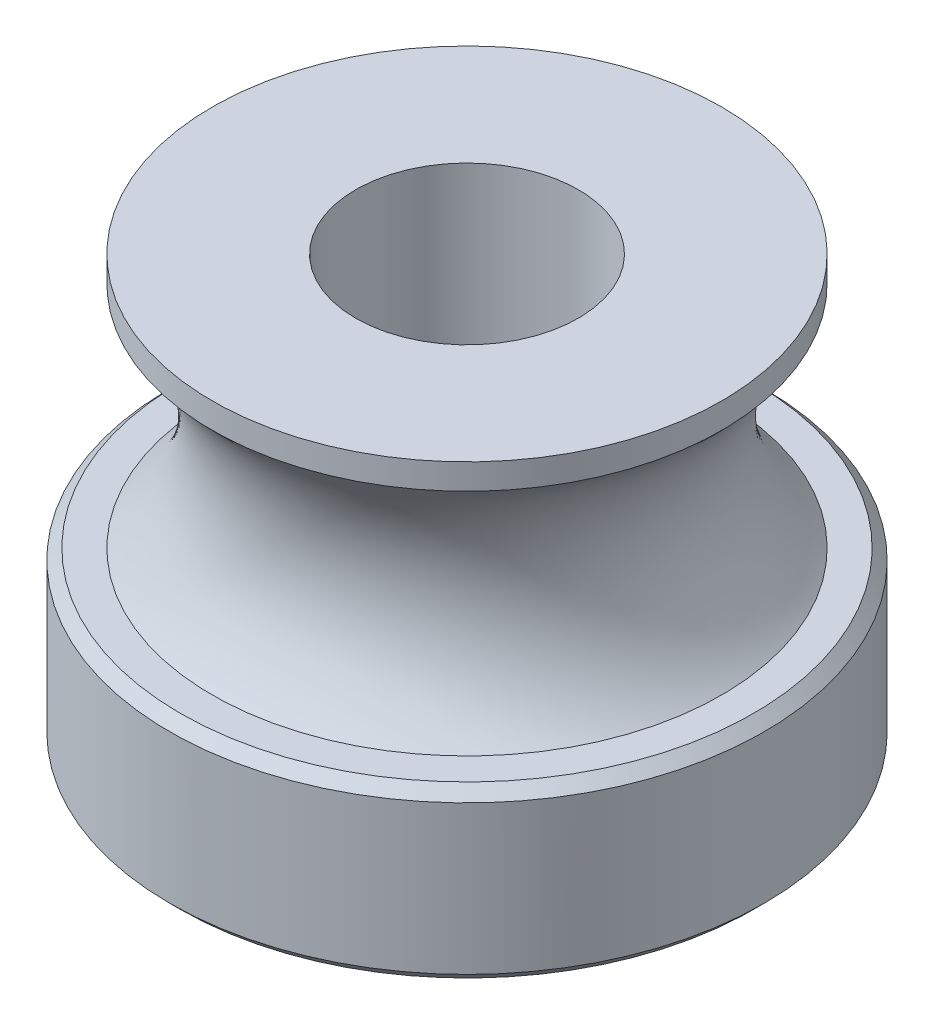
SolidWorks part; units mm, degrees
material "Brass"
ref_plane "Front Plane" through (0, 0, 0) normal (0, 0, 1) x (1, 0, 0)
ref_plane "Top Plane" through (0, 0, 0) normal (0, 1, 0) x (1, 0, 0)
ref_plane "Right Plane" through (0, 0, 0) normal (1, 0, 0) x (0, 0, -1)
sketch "Sketch1" plane through (0, 0, 0) normal (0, 0, 1) x (1, 0, 0)
  line L0 (0, 0) -> (0, 7.9375) construction
  line L1 (0, 7.9375) -> (-4.7625, 7.9375)
  line L2 (-5.5562, 3.175) -> (-5.5562, 0)
  line L3 (-5.5562, 0) -> (0, 0)
  line L4 (0, 0) -> (0, 7.9375)
  line L5 (0, 0) -> (0, -2.6189) construction
  line L6 (-3.81, 3.175) -> (-3.81, 7.9375) construction
  line L7 (-5.5562, 3.175) -> (-4.7625, 3.175)
  line L10 (-4.7625, 7.9375) -> (-4.7625, 7.4612)
  arc A0 (-4.7625, 3.175) -> (-4.7625, 7.4612) centre (-6.6973, 5.3181) ccw
  point P1 (0, 3.9688)
  dimension "D1" = 0.4763
  dimension "D2" = 0.9525
revolve "Revolve1" add sketch "Sketch1" angle 360 about L0
sketch "Sketch3" plane through (0, 0, 0) normal (0, 1, 0) x (1, 0, 0)
  circle A0 centre (0, 0) radius 2.0828
extrude "Cut-Extrude1" cut sketch "Sketch3" along normal through all
sketch "Sketch4" plane through (0, 0, 0) normal (0, 1, 0) x (1, 0, 0)
  circle A1 centre (0, 0) radius 2.0828
  circle A2 centre (0, 0) radius 2.0828
  dimension "D1" = 0
curve "Helix/Spiral1" pitch 0.7937 height 14.2875 turns 18 parameters "pitch"=0.7937
sketch "Sketch21" plane through (0, 0, 0) normal (0, 1, 0) x (1, 0, 0)
  line L0 (0, 2.0828) -> (0, 5.5562)
  circle A0 centre (0, 0) radius 5.5562 construction
  circle A1 centre (0, 0) radius 2.0828 construction
  circle A2 centre (0, 0) radius 5.5562 construction
  circle A3 centre (0, 0) radius 2.0828 construction
  dimension "D1" = 3.4734
sketch "Sketch5" plane through (0, 0, 0) normal (1, 0, 0) x (0, 0, -1)
  line L0 (-2.0828, 0) -> (-2.0828, -0.6945)
  line L1 (-2.0828, -0.6945) -> (-1.5672, -0.3969)
  line L2 (-1.5672, -0.3969) -> (-1.5672, -0.2977)
  line L3 (-1.5672, -0.2977) -> (-2.0828, 0)
  line L4 (-1.5672, -0.3473) -> (-2.0828, -0.3473) construction
  line L5 (-1.825, -0.5457) -> (-1.825, -0.1488) construction
  line L6 (2.0828, 0) -> (-2.0828, 0) construction
  dimension "D1" = 0.0992
  dimension "D2" = 0.3969
  dimension "D3" = 60
sweep "Sweep1" [suppressed] add profiles "Sketch5" path "Helix/Spiral1"
sketch "Sketch13" plane through (0, 0, 0) normal (0, -1, 0) x (1, 0, 0)
  circle A1 centre (0, 0) radius 5.5562
  circle A2 centre (0, 0) radius 5.5562
  dimension "D1" = 0
extrude "Cut-Extrude2" [suppressed] cut sketch "Sketch13" along normal through all
sketch "Sketch14" plane through (0, 7.9375, 0) normal (0, 1, 0) x (1, 0, 0)
  circle A0 centre (0, 0) radius 5.5562 construction
  circle A1 centre (0, 0) radius 5.5562
extrude "Cut-Extrude3" [suppressed] cut sketch "Sketch14" along normal through all
sketch "Sketch15" plane through (0, 0, 0) normal (0, -1, 0) x (1, 0, 0)
  circle A0 centre (0, 0) radius 2.0828 construction
  circle A1 centre (0, 0) radius 2.0828
extrude "Cut-Extrude4" [suppressed] cut sketch "Sketch15" against normal through all draft 45
sketch "Sketch16" plane through (0, 7.9375, 0) normal (0, 1, 0) x (1, 0, 0)
  circle A0 centre (0, 0) radius 2.0828 construction
  circle A1 centre (0, 0) radius 2.0828
extrude "Cut-Extrude5" [suppressed] cut sketch "Sketch16" against normal through all draft 45
chamfer "Chamfer1" distance 0.1984 angle 45 2 edges at (0, 3.175, -5.5562) (0, 0, -5.5562)
sketch "Sketch11" [suppressed] plane through (0, 0, 0) normal (0, 0, 1) x (1, 0, 0)
  line L0 (-2.0828, 7.9375) -> (-2.0828, 0)
  line L1 (2.0828, 7.9375) -> (2.0828, 0)
  line L2 (4.7625, 7.9375) -> (-4.7625, 7.9375) construction
  line L4 (-2.0828, 0) -> (2.0828, 0) construction
  dimension "D1" = 4.1656
sketch "Sketch12" plane through (0, 0, 0) normal (1, 0, 0) x (0, 0, -1)
  line L0 (-2.0828, 7.9375) -> (-2.0828, 0)
  line L1 (2.0828, 7.9375) -> (2.0828, 0)
  line L2 (-2.0828, 0) -> (2.0828, 0) construction
  line L3 (4.7625, 7.9375) -> (-4.7625, 7.9375) construction
  line L5 (-5.3578, 0) -> (5.3578, 0) construction
  dimension "D1" = 4.1656
ref_plane "Plane1" through (0, 0, -12.7) normal (0, 0, 1) x (1, 0, 0)
sketch "Sketch17" [suppressed] plane through (0, 0, -12.7) normal (0, 0, 1) x (1, 0, 0)
  line L0 (-0.127, 0.1984) -> (-0.127, 2.9766)
  line L1 (5.5562, 0.1984) -> (-5.5562, 0.1984) construction
  line L2 (5.5562, 2.9766) -> (-5.5562, 2.9766) construction
  line L3 (0.127, 0.1984) -> (0.127, 2.9766)
  line L4 (0, 0.1984) -> (0, 2.9766) construction
  line L5 (-0.127, 0.1984) -> (0.127, 0.1984)
  line L6 (-0.127, 2.9766) -> (0.127, 2.9766)
  line L7 (0, 1.5875) -> (6.048, 1.5875) construction
  line L8 (0, 1.5875) -> (0, 0) construction
  dimension "D1" = 0
  dimension "D2" = 0.254
extrude "Cut-Extrude6" [suppressed] cut sketch "Sketch17" along normal offset from surface (7.2722 mm away) 0.127 up to face at (0, 2.9766, -5.5562) offset beyond the face yes
pattern_circular "CirPattern1" [suppressed] count 72 over 360 of bodies 116
sketch "Sketch18" [suppressed] plane through (0, 7.9375, 0) normal (0, 1, 0) x (1, 0, 0)
  circle A0 centre (0, 0) radius 5.5562
  arc A2 (1.5604, 5.3327) -> (1.315, 5.3984) centre (0, 0) ccw construction
ref_plane "Plane3" through (0, 3.9688, 0) normal (0, 1, 0) x (-1, 0, 0)
equation "\"D1@Sketch5\" = \"pitch@Helix/Spiral1\"*.125"
equation "\"D2@Sketch5\" = \"pitch@Helix/Spiral1\"*.5"
equation "\"D1@Sketch11\" = \"OD@Sketch3\""
equation "\"D1@Sketch12\" = \"OD@Sketch3\""
equation "\"D1@Chamfer1\" = \"pitch@Helix/Spiral1\"*.25"
equation "\"D3@Helix/Spiral1\" = \"B@Sketch1\"+.250"
equation "\"D1@Sketch1\" = \"D@Sketch1\"/10"
equation "\"D2@Sketch1\" = \"C@Sketch1\"*.1"
